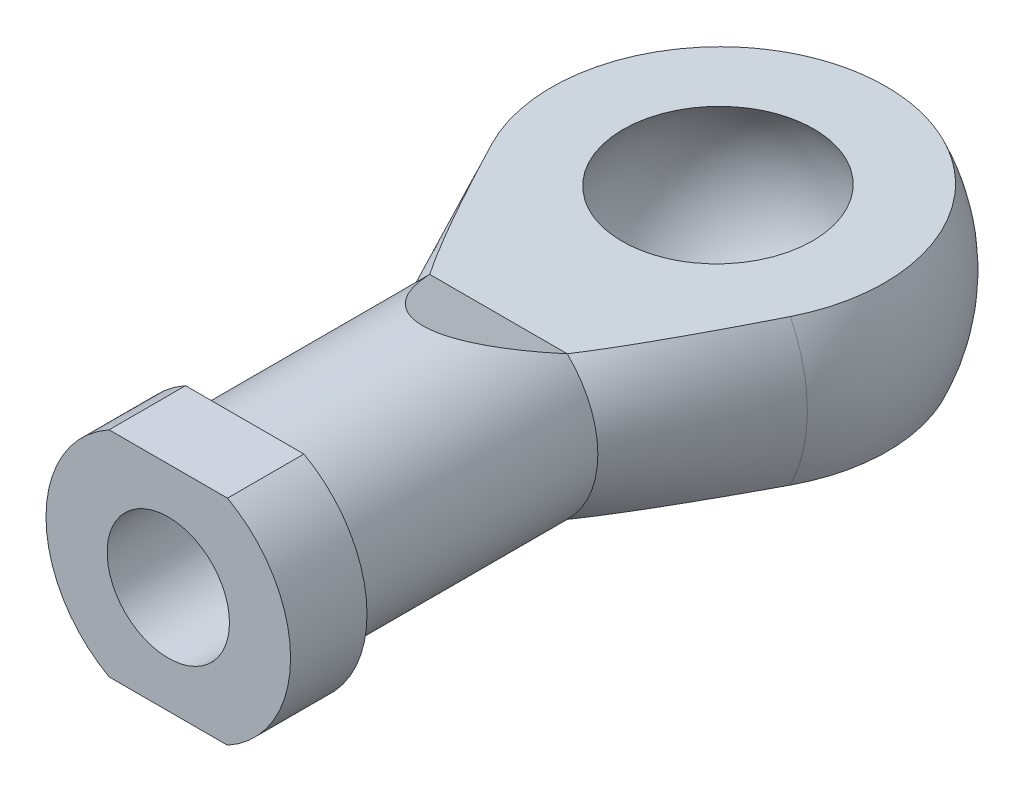
SolidWorks part; units mm, degrees
ref_plane "Płaszczyzna przednia" through (0, 0, 0) normal (0, 0, 1) x (1, 0, 0)
ref_plane "Płaszczyzna górna" through (0, 0, 0) normal (0, 1, 0) x (1, 0, 0)
ref_plane "Płaszczyzna prawa" through (0, 0, 0) normal (1, 0, 0) x (0, 0, -1)
sketch "Szkic1" plane through (0, 0, 0) normal (0, 1, 0) x (1, 0, 0)
  line L0 (-6.5, 21.6) -> (-10.8757, 30.9286)
  line L1 (-8, 0) -> (-8, 5)
  line L2 (-6.5, 5) -> (-6.5, 21.6)
  line L3 (-8, 5) -> (-6.5, 5)
  line L4 (-8, 0) -> (0, 0)
  line L5 (0, 43.9) -> (0, 48)
  line L6 (0, 0) -> (0, 28.1)
  arc A0 (0, 48) -> (-10.8757, 30.9286) centre (0, 36) ccw
  arc A1 (0, 43.9) -> (0, 28.1) centre (0, 36) ccw
revolve "Obrót2" add sketch "Szkic1" angle 360 about L6
sketch "Szkic2" plane through (0, 0, 0) normal (1, 0, 0) x (0, 0, -1)
  line L0 (-3.907, 7) -> (15.2853, 7)
  line L1 (15.2853, 7) -> (21.6, 4.6922)
  line L2 (21.6, 6.5) -> (21.6, -6.5) construction
  line L3 (21.6, 4.6922) -> (53.3737, 4.9748)
  line L4 (53.3737, 4.9748) -> (53.3737, 17.1778)
  line L5 (53.3737, 17.1778) -> (-3.907, 17.1778)
  line L6 (-3.907, 17.1778) -> (-3.907, 7)
  line L7 (0, 0) -> (-13.3821, 0) construction
  line L8 (0, 8) -> (0, -8) construction
  line L9 (-3.907, -17.1778) -> (-3.907, -7)
  line L10 (53.3737, -17.1778) -> (-3.907, -17.1778)
  line L11 (53.3737, -4.9748) -> (53.3737, -17.1778)
  line L12 (21.6, -4.6922) -> (53.3737, -4.9748)
  line L13 (15.2853, -7) -> (21.6, -4.6922)
  line L14 (-3.907, -7) -> (15.2853, -7)
  dimension "D1" = 4.5
  dimension "D2" = 7
extrude "Wytnij-wyciągnięcie4" cut sketch "Szkic2" against normal through all both and the other way through all
sketch "Szkic3" plane through (0, 0, 0) normal (0, 0, 1) x (1, 0, 0)
  circle A0 centre (0, 0) radius 4
  dimension "D1" = 8
extrude "Wytnij-wyciągnięcie5" cut sketch "Szkic3" against normal blind 16
